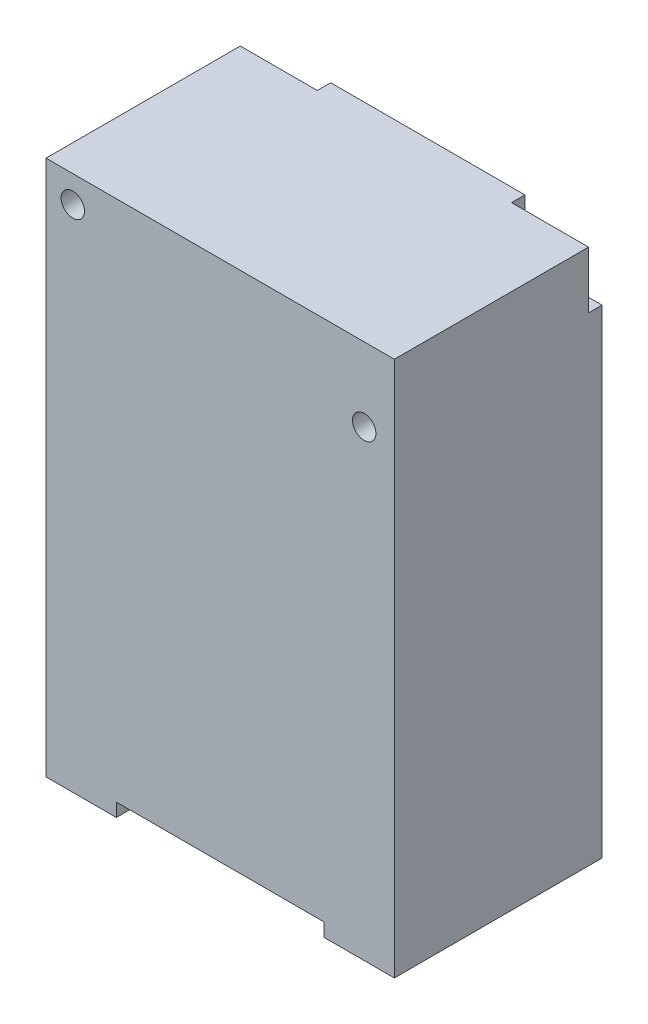
SolidWorks part; units mm, degrees
ref_plane "Plan de face" through (0, 0, 0) normal (0, 0, 1) x (1, 0, 0)
ref_plane "Plan de dessus" through (0, 0, 0) normal (0, 1, 0) x (1, 0, 0)
ref_plane "Plan de droite" through (0, 0, 0) normal (1, 0, 0) x (0, 0, -1)
sketch "Esquisse1" plane through (0, 0, 0) normal (0, 0, 1) x (1, 0, 0)
  line L0 (21.5, 40) -> (21.5, 29) construction
  line L1 (26, -40) -> (-26, -40)
  line L2 (26, -40) -> (26, 40)
  line L3 (26, 40) -> (-26, 40)
  line L4 (-26, -40) -> (-26, 40)
  line L5 (26, -40) -> (-26, 40) construction
  line L6 (26, 40) -> (-26, -40) construction
  line L7 (21.5, 29) -> (26, 29) construction
  line L9 (-26, 40) -> (-22, 40) construction
  line L10 (-26, 40) -> (-26, 36) construction
  line L11 (-26, 36) -> (-22, 36) construction
  line L12 (-22, 40) -> (-22, 36) construction
  circle A0 centre (21.5, 29) radius 1.75
  circle A1 centre (-22, 36) radius 1.75
  point P0 (0, 0)
  dimension "D5" = 3.5
  dimension "D1" = 80
  dimension "D2" = 52
  dimension "D3" = 4.5
  dimension "D4" = 11
  dimension "D6" = 4
extrude "Boss.-Extru.1" add sketch "Esquisse1" along normal blind 31
sketch "Esquisse3" plane through (0, -40, 0) normal (0, -1, 0) x (1, 0, 0)
  line L0 (-26, 31) -> (26, 31) construction
  line L1 (15.5, 16) -> (-15.5, 16)
  line L2 (15.5, 16) -> (15.5, 31)
  line L3 (15.5, 31) -> (-15.5, 31)
  line L4 (-15.5, 16) -> (-15.5, 31)
  line L5 (15.5, 16) -> (-15.5, 31) construction
  line L6 (15.5, 31) -> (-15.5, 16) construction
  point P0 (0, 23.5)
  dimension "D1" = 15
  dimension "D2" = 31
extrude "Enlèv. mat.-Extru.3" cut sketch "Esquisse3" against normal blind 2
extrude "Boss.-Extru.3" add sketch "Esquisse1<2>" along normal blind 25 contours A0 | A1 region at (21.5, 29, 0)
sketch "Esquisse1<2>" plane through (0, 0, 0) normal (0, 0, 1) x (1, 0, 0) same geometry as "Esquisse1"
sketch "Esquisse2" plane through (0, 0, 0) normal (0, 0, -1) x (-1, 0, 0)
  line L0 (0, 0) -> (0, 40) construction
  line L1 (-26, 40) -> (-14.5, 40)
  line L2 (-26, 40) -> (-26, 31.5)
  line L3 (-26, 31.5) -> (-14.5, 31.5)
  line L4 (-14.5, 40) -> (-14.5, 31.5)
  line L5 (-26, 40) -> (26, 40) construction
  line L6 (14.5, 40) -> (14.5, 31.5)
  line L7 (26, 31.5) -> (14.5, 31.5)
  line L8 (26, 40) -> (26, 31.5)
  line L9 (26, 40) -> (14.5, 40)
  dimension "D1" = 8.5
  dimension "D2" = 11.5
extrude "Enlèv. mat.-Extru.1" cut sketch "Esquisse2" against normal blind 2
